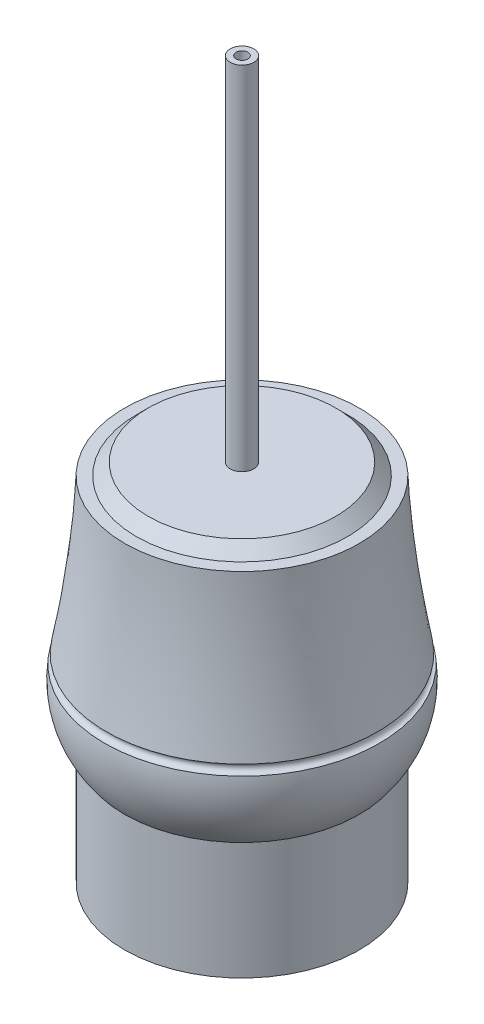
SolidWorks part; units mm, degrees
ref_plane "Front Plane" through (0, 0, 0) normal (0, 0, 1) x (1, 0, 0)
ref_plane "Top Plane" through (0, 0, 0) normal (0, 1, 0) x (1, 0, 0)
ref_plane "Right Plane" through (0, 0, 0) normal (1, 0, 0) x (0, 0, -1)
sketch "Sketch2" plane through (0, 0, 0) normal (0, 1, 0) x (1, 0, 0)
  circle A0 centre (0, 0) radius 10
extrude "Boss-Extrude1" add sketch "Sketch2" along normal blind 10
sketch "Sketch3" plane through (0, 10, 0) normal (0, 1, 0) x (1, 0, 0)
  circle A0 centre (0, 0) radius 13
ref_plane "Plane1" through (0, 30, 0) normal (0, 1, 0) x (1, 0, 0)
sketch "Sketch4" plane through (0, 30, 0) normal (0, 1, 0) x (1, 0, 0)
  circle A0 centre (0, 0) radius 10
loft "Loft1" add profiles "Sketch3", "Sketch4" connector at (-12.8603, 10, 1.901) connector at (-9.0796, 30, -4.1906)
fillet "Fillet1" radius 8 1 edges at (0, 10, 13)
sketch "Sketch5" plane through (0, 0, 0) normal (1, 0, 0) x (0, 0, -1)
  line L0 (0, 16.4897) -> (0, 16.8281) construction
  line L1 (-11.6337, 16.4897) -> (11.6337, 16.4897) construction
  circle A0 centre (-11.6337, 16.4897) radius 0.4
  spline S0 degree 3 poles (-10, 30) (-10.0012, 29.9739) (-10.0034, 29.9226) (-10.009, 29.7993) (-10.017, 29.6309) (-10.0278, 29.4152) (-10.0366, 29.2478) (-10.0423, 29.143) (-10.0452, 29.0911) (-10.0485, 29.0321) (-10.0529, 28.9546) (-10.0578, 28.8698) (-10.0636, 28.7696) (-10.0705, 28.6547) (-10.0785, 28.5245) (-10.0859, 28.4089) (-10.0916, 28.3195) (-10.0957, 28.2579) (-10.1013, 28.1724) (-10.1103, 28.0385) (-10.1297, 27.7605) (-10.1478, 27.5142) (-10.1648, 27.2928) (-10.1725, 27.1946) (-10.1805, 27.0931) (-10.1874, 27.0075) (-10.1938, 26.9283) (-10.2001, 26.8515) (-10.2064, 26.7768) (-10.2131, 26.6965) (-10.22, 26.6164) (-10.2263, 26.5427) (-10.2312, 26.4863) (-10.2435, 26.3462) (-10.2644, 26.1129) (-10.2889, 25.8507) (-10.3058, 25.6751) (-10.3143, 25.5871) (-10.3219, 25.5099) (-10.3311, 25.4171) (-10.3405, 25.3224) (-10.3495, 25.2327) (-10.3577, 25.1523) (-10.3663, 25.0694) (-10.3752, 24.9839) (-10.3843, 24.8977) (-10.3939, 24.8074) (-10.4028, 24.7243) (-10.4168, 24.5949) (-10.4385, 24.3967) (-10.4657, 24.1554) (-10.4915, 23.931) (-10.508, 23.7908) (-10.5205, 23.6853) (-10.5334, 23.5771) (-10.5515, 23.4268) (-10.5674, 23.2974) (-10.5761, 23.227) (-10.5809, 23.1885) (-10.5884, 23.1283) (-10.5988, 23.0453) (-10.6097, 22.9595) (-10.6463, 22.6716) (-10.7223, 22.0922) (-10.8494, 21.1836) (-11.0304, 19.9761) (-11.2054, 18.8996) (-11.3419, 18.1061) (-11.3996, 17.7777) (-11.4332, 17.5879) (-11.4568, 17.456) (-11.5217, 17.0942) (-11.5792, 16.7842) (-11.6337, 16.4897) knots 0 0 0 0 0.005749 0.011303 0.027146 0.04281 0.059017 0.063912 0.066124 0.070446 0.076928 0.083197 0.089141 0.099156 0.108667 0.117746 0.124767 0.12857 0.13136 0.143622 0.158097 0.19265 0.197931 0.206946 0.2143 0.220395 0.226215 0.231848 0.237329 0.242697 0.249759 0.25531 0.259054 0.262211 0.286248 0.310569 0.320132 0.325052 0.330011 0.337176 0.345669 0.35144 0.357335 0.363421 0.369758 0.376376 0.383087 0.389902 0.394741 0.411721 0.433748 0.448174 0.461395 0.464813 0.471511 0.485478 0.498246 0.500052 0.501432 0.506742 0.513429 0.519822 0.525768 0.577245 0.648371 0.727565 0.8458 0.888256 0.904667 0.919136 0.930652 0.934132 1 1 1 1 construction
revolve "Cut-Revolve1" cut sketch "Sketch5" angle 360 about L0
sketch "Sketch6" plane through (0, 30, 0) normal (0, 1, 0) x (1, 0, 0)
  circle A0 centre (0, 0) radius 9
extrude "Boss-Extrude2" add sketch "Sketch6" along normal blind 1
chamfer "Chamfer1" distance 1 angle 45 1 edges at (0, 31, 9)
sketch "Sketch7" plane through (0, 31, 0) normal (0, 1, 0) x (1, 0, 0)
  circle A0 centre (0, 0) radius 1
extrude "Boss-Extrude3" add sketch "Sketch7" along normal blind 30
sketch "Sketch8" plane through (0, 61, 0) normal (0, 1, 0) x (1, 0, 0)
  circle A0 centre (0, 0) radius 0.5
extrude "Cut-Extrude1" cut sketch "Sketch8" against normal blind 1
